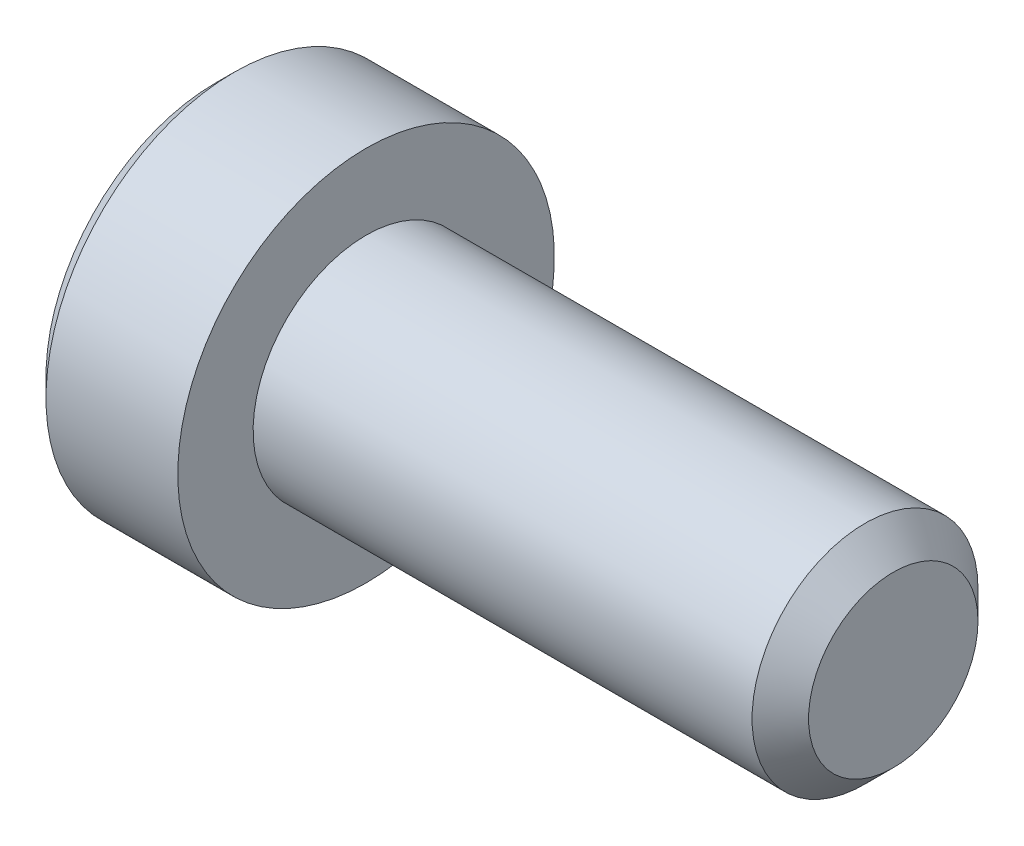
SolidWorks part; units mm, degrees
ref_plane "Front Plane" through (0, 0, 0) normal (0, 0, 1) x (1, 0, 0)
ref_plane "Top Plane" through (0, 0, 0) normal (0, 1, 0) x (1, 0, 0)
ref_plane "Right Plane" through (0, 0, 0) normal (1, 0, 0) x (0, 0, -1)
sketch "Sketch1" plane through (0, 0, 0) normal (0, 0, 1) x (1, 0, 0)
  line L0 (7, 0) -> (-7, 0) construction
  line L1 (7, 3) -> (7, -3) construction
  line L2 (-7, 5) -> (-7, -5) construction
  line L3 (-7, 5) -> (-10.5, 5) construction
  line L4 (-10.5, 5) -> (-11, 4.5) construction
  line L5 (-11, 4.5) -> (-11, -4.5) construction
  line L6 (-11, -4.5) -> (-10.5, -5) construction
  line L7 (-10.5, -5) -> (-7, -5) construction
  point P7 (-7.88, 0)
  point P12 (3, -3)
  dimension "D1" = 45
  dimension "Dec." = 6
  dimension "Length" = 14
  dimension "Head Dia" = 10
  dimension "Head Height" = 4
  dimension "Hex Depth" = 3.12
  dimension "Chamfer" = 0.5
  dimension "D2" = 4
ref_plane "Plane1" through (7, 0, 0) normal (1, 0, 0) x (0, 0, -1)
ref_plane "Plane2" through (-11, 0, 0) normal (1, 0, 0) x (0, 0, -1)
sketch "Sketch2" plane through (7, 0, 0) normal (1, 0, 0) x (0, 0, -1)
  circle A0 centre (0, 0) radius 3
extrude "Boss-Extrude1" add sketch "Sketch2" against normal up to vertex (14 mm away) up to point (-7, 0, 0)
sketch "Sketch3" plane through (7, 0, 0) normal (1, 0, 0) x (0, 0, -1)
  circle A0 centre (0, 0) radius 3 construction
  circle A1 centre (0, 0) radius 3
curve "Helix/Spiral1" pitch 1 height 15 turns 15 parameters "Pitch"=1
chamfer "Chamfer1" distance 0.75 angle 45 1 edges at (7, 0, -3)
sketch "Sketch5" plane through (0, 0, 0) normal (0, 0, 1) x (1, 0, 0)
  line L0 (6.5625, 3) -> (7.4375, 3)
  line L1 (7.4375, 3) -> (7.0625, 2.3505)
  line L2 (7.0625, 2.3505) -> (6.9375, 2.3505)
  line L3 (6.9375, 2.3505) -> (6.5625, 3)
  line L4 (7, 2.3505) -> (7, 3) construction
  line L5 (6.75, 2.6752) -> (7.25, 2.6752) construction
  dimension "D1" = 60
  dimension "D2" = 0.5
  dimension "D3" = 0.125
sweep "Cut-Sweep1" [suppressed] cut profiles "Sketch5" path "Helix/Spiral1"
sketch "Sketch4" plane through (-11, 0, 0) normal (1, 0, 0) x (0, 0, -1)
  line L0 (-5, 0.7937) -> (5, 0.7937) construction
  line L1 (0, 2.3094) -> (-2, 1.1547)
  line L2 (-2, 1.1547) -> (-2, -1.1547)
  line L3 (-2, -1.1547) -> (0, -2.3094)
  line L4 (0, -2.3094) -> (2, -1.1547)
  line L5 (2, -1.1547) -> (2, 1.1547)
  line L6 (2, 1.1547) -> (0, 2.3094)
  line L7 (0, 0) -> (0, 0.7937) construction
  circle A0 centre (0, 0) radius 2 construction
  dimension "Hex Size" = 4
  dimension "D1" = 10
  dimension "D2" = 0.7937
sketch "Sketch6" plane through (0, 0, 0) normal (0, 0, 1) x (1, 0, 0)
  line L0 (-10.5, 5) -> (-11, 4.5) construction
  line L1 (-7, 5) -> (-10.5, 5) construction
  line L2 (-7, 5) -> (-7, -5) construction
  line L3 (-11, 4.5) -> (-11, -4.5) construction
  line L4 (-10.5, 5) -> (-11, 4.5)
  line L5 (-7, 5) -> (-10.5, 5)
  line L6 (-7, 5) -> (-7, 0)
  line L7 (-11, 4.5) -> (-11, 0)
  line L8 (-7, 0) -> (-11, 0) construction
  line L9 (-7, 0) -> (-11, 0)
revolve "Revolve1" add sketch "Sketch6" angle 360 about L8
extrude "Cut-Extrude1" cut sketch "Sketch4" along normal up to vertex (3.12 mm away) up to point (-7.88, 0, 0)
sketch "Sketch8" plane through (-11, 0, 0) normal (-1, 0, 0) x (0, 0, 1)
  circle A1 centre (0, 0) radius 2.3094
extrude "Cut-Extrude2" cut sketch "Sketch8" against normal through all draft 45
equation "\"D3@Helix/Spiral1\" = \"Length@Sketch1\"+\"Pitch@Helix/Spiral1\""
equation "\"D3@Sketch5\" = \"Pitch@Helix/Spiral1\"*.125"
equation "\"D2@Sketch5\" = \"Pitch@Helix/Spiral1\"*.50"
equation "\"D1@Chamfer1\" = \"Pitch@Helix/Spiral1\"*.75"
equation "\"D2@Sketch1\" = \"Pitch@Helix/Spiral1\"*4"
equation "\"D1@Sketch4\" = \"Head Dia@Sketch1\""
equation "\"Chamfer@Sketch1\" = \"Head Height@Sketch1\"/8"
